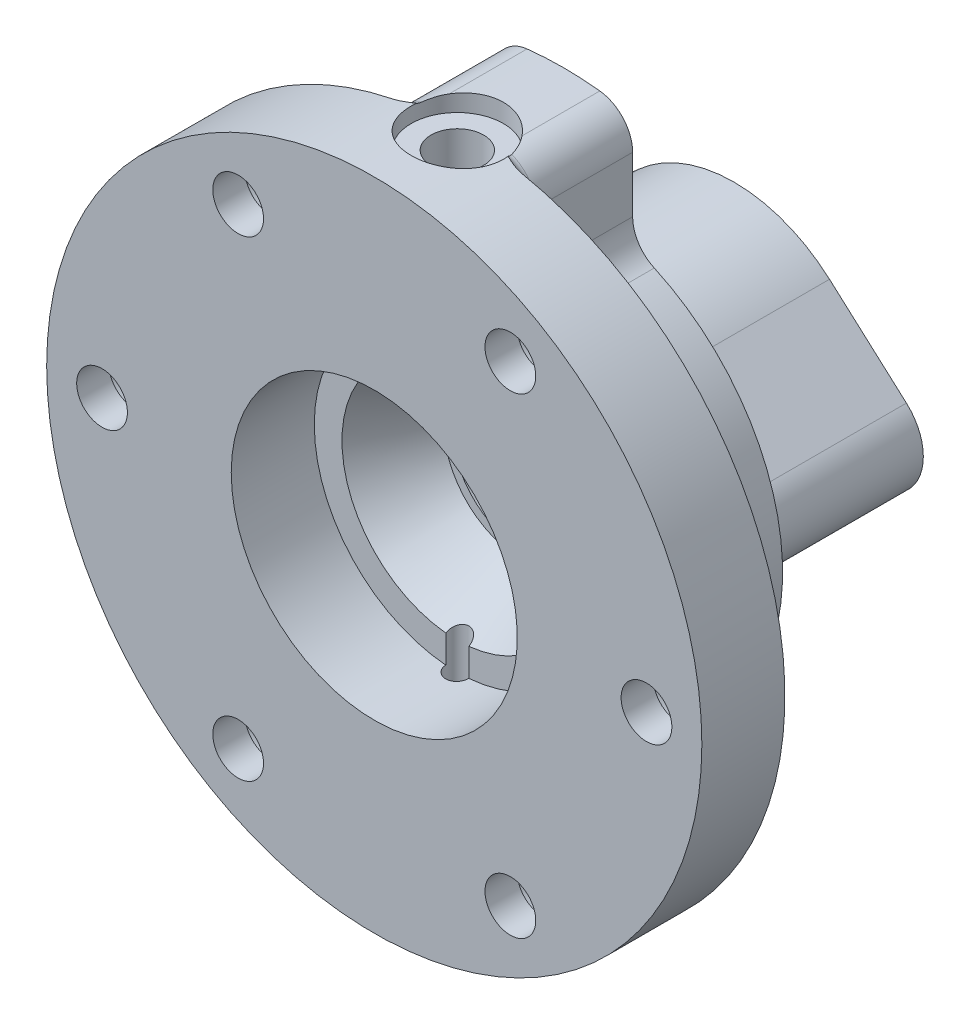
SolidWorks part; units mm, degrees
ref_plane "Piano frontale" through (0, 0, 0) normal (0, 0, 1) x (1, 0, 0)
ref_plane "Piano superiore" through (0, 0, 0) normal (0, 1, 0) x (1, 0, 0)
ref_plane "Piano destro" through (0, 0, 0) normal (1, 0, 0) x (0, 0, -1)
sketch "Schizzo1" plane through (0, 0, 0) normal (0, 1, 0) x (1, 0, 0)
  line L0 (0, 44.9759) -> (0, -36.1533) construction
  line L1 (-15.5, 0) -> (-35.5, 0)
  line L2 (-55, 0) -> (55, 0) construction
  line L3 (-35.5, 0) -> (-35.5, 20.5)
  line L4 (-35.5, 20.5) -> (-7.5, 20.5)
  line L5 (-7.5, 20.5) -> (-7.5, 16)
  line L6 (-7.5, 16) -> (-8.4585, 16)
  line L7 (-8.4585, 16) -> (-12.5, 9)
  line L8 (-12.5, 9) -> (-15.5, 9)
  line L9 (-15.5, 9) -> (-15.5, 0)
  point P3 (-11.0457, 18.3109)
  point P7 (-12.3203, 13.9449)
  dimension "D1" = 15
  dimension "D2" = 20.5
  dimension "D3" = 7
  dimension "D4" = 30
  dimension "D5" = 25
  dimension "D6" = 31
  dimension "D7" = 71
  dimension "D8" = 9
revolve "Rivoluzione1" add sketch "Schizzo1" angle 360 about L0
sketch "Schizzo3" plane through (0, 0, -20.5) normal (0, 0, -1) x (-1, 0, 0)
  line L0 (0, 35.5) -> (0, -35.5) construction
  line L1 (-7.5, 34.6987) -> (-7.5, 22.5347)
  line L2 (-7.5, -22.5347) -> (-7.5, -34.6987)
  circle A0 centre (0, 0) radius 35.5 construction
  arc A1 (-7.5, 22.5347) -> (-7.5, -22.5347) centre (0, 0) ccw
  point P9 (0, 0)
  circle M3 centre (0, 0) radius 35.5
  dimension "D2" = 47.5
  dimension "D1" = 15
extrude "Taglio-Estrusione1" cut sketch "Schizzo3" against normal blind 11.5 and the other way through all contours A1 L1 L2 M3 region at (8.2483, 28.6167, -20.5)
mirror "Specchia1" about plane through (0, 0, 0) normal (1, 0, 0) of "Taglio-Estrusione1"
sketch "Schizzo4" plane through (0, 0, -20.5) normal (0, 0, -1) x (-1, 0, 0)
  line L0 (-23.75, 0) -> (23.75, 0) construction
  line L5 (0, 0) -> (0, -20.8425) construction
  line L6 (-18.6667, 4.0995) -> (-10.3333, 11.553)
  line L7 (18.6667, 4.0995) -> (10.3333, 11.553)
  line L8 (18.6667, -4.0995) -> (10.3333, -11.553)
  line L10 (-18.6667, -4.0995) -> (-10.3333, -11.553)
  arc A0 (-7.5, 22.5347) -> (-7.5, -22.5347) centre (0, 0) ccw construction
  arc A1 (7.5, -22.5347) -> (7.5, 22.5347) centre (0, 0) ccw construction
  circle A2 centre (0, 0) radius 11.5
  arc A7 (-10.3333, -11.553) -> (10.3333, -11.553) centre (0, 0) ccw
  arc A8 (-18.6667, 4.0995) -> (-18.6667, -4.0995) centre (-15, 0) ccw
  arc A9 (18.6667, 4.0995) -> (18.6667, -4.0995) centre (15, 0) cw
  arc A10 (10.3333, 11.553) -> (-10.3333, 11.553) centre (0, 0) ccw
  point P11 (18.6667, -4.0995)
  point P19 (-10.2774, 11.6028)
  point P24 (18.7896, -4.0995)
  point P27 (-19.3805, 3.3258)
  dimension "D1" = 23
  dimension "D2" = 31
  dimension "D3" = 5.5
  dimension "D4" = 30
extrude "Estrusione-Estrusione1" add sketch "Schizzo4" along normal blind 18.5
fillet "Raccordo1" radius 4 8 edges at (-7.5, -34.6987, -14.75) (-7.5, -22.5347, -14.75) (7.5, -34.6987, -14.75) (7.5, -22.5347, -14.75) (7.5, 22.5347, -14.75) (7.5, 34.6987, -14.75) (-7.5, 34.6987, -14.75) (-7.5, 22.5347, -14.75)
fillet "Raccordo2" radius 1 14 edges at (8.1362, 23.0905, -9) (7.5, 28.28, -9) (6.4814, 33.9716, -9) (-6.4814, 33.9716, -9) (-7.5, 28.28, -9) (-8.1362, 23.0905, -9) (6.4814, -33.9716, -9) (7.5, -28.28, -9) (8.1362, -23.0905, -9) (-6.4814, -33.9716, -9) (-7.5, -28.28, -9) (-8.1362, -23.0905, -9) (-23.75, 0, -9) (23.75, 0, -9)
fillet "Raccordo3" radius 2 8 edges at (20.5, 0, -20.5) (14.5, -7.8262, -20.5) (0, 15.5, -20.5) (14.5, 7.8262, -20.5) (-14.5, 7.8262, -20.5) (-20.5, 0, -20.5) (-14.5, -7.8262, -20.5) (0, -15.5, -20.5)
hole_wizard "Foro Ø5.0 (5)-1" positions "Schizzo6" profile "Schizzo7" hole size "Ø5.0" standard "ISO"
sketch "Schizzo6" plane through (0, 0, -39) normal (0, 0, -1) x (-1, 0, 0)
  point P0 (-15, 0)
  point P3 (15, 0)
sketch "Schizzo7" plane through (15, 0, -39) normal (1, 0, 0) x (0, 1, 0)
  line L0 (0, 0) -> (0, 9.0022)
  line L1 (0, 9.0022) -> (2.5, 7.5)
  line L2 (2.5, 7.5) -> (2.5, 0.025)
  line L3 (2.5, 0.025) -> (2.525, 0)
  line L5 (2.525, 0) -> (0, 0)
  line L6 (-2.5, 0.025) -> (-2.525, 0) construction
  line L10 (0, 9.0022) -> (-2.5, 7.5) construction
  line L11 (0, -6.35) -> (0, 107.95) construction
  dimension "Hole Dia." = 5
  dimension "Hole Depth" = 7.5
  dimension "Near C'Sink Dia." = 5.05
  dimension "Near C'Sink Angle" = 90
  dimension "Drill Angle" = 118
ref_point "Punto1"
ref_plane "Piano2" through (0, -35.5, 0) normal (0, 1, 0) x (1, 0, 0)
hole_wizard "Foro Ø2.5 (2.5)-1" positions "Schizzo9" profile "Schizzo10" hole size "Ø2.5" standard "ISO"
sketch "Schizzo9" plane through (0, -35.5, 0) normal (0, 1, 0) x (1, 0, 0)
  line L0 (0, 0) -> (0, 11.1259) construction
  line L1 (-35.5, 0) -> (35.5, 0) construction
  point P6 (0, 9)
  dimension "D1" = 9
sketch "Schizzo10" plane through (0, -35.5, -9) normal (1, 0, 0) x (0, 0, -1)
  line L0 (0, 0) -> (0, 36.2501)
  line L1 (0, 36.2501) -> (1.25, 35.499)
  line L2 (1.25, 35.499) -> (1.25, 0.025)
  line L3 (1.25, 0.025) -> (1.275, 0)
  line L5 (1.275, 0) -> (0, 0)
  line L6 (-1.25, 0.025) -> (-1.275, 0) construction
  line L10 (0, 36.2501) -> (-1.25, 35.499) construction
  line L11 (0, -6.35) -> (0, 107.95) construction
  dimension "Hole Dia." = 2.5
  dimension "Hole Depth" = 35.499
  dimension "Near C'Sink Dia." = 2.55
  dimension "Near C'Sink Angle" = 90
  dimension "Drill Angle" = 118
hole_wizard "Foro lamato per Bullone M5 a testa esagonale-1" positions "Schizzo11" profile "Schizzo12" counterbore size "M5" standard "ISO"
sketch "Schizzo11" plane through (0, -35.5, 0) normal (0, 1, 0) x (1, 0, 0)
  line L0 (-15.5, 9) -> (15.5, 9) construction
  point P0 (0, 9)
sketch "Schizzo12" plane through (0, -35.5, -9) normal (1, 0, 0) x (0, 0, -1)
  line L0 (0, 0) -> (0, 17.7125)
  line L1 (0, 17.7125) -> (2.85, 16)
  line L2 (2.85, 16) -> (2.85, 2)
  line L3 (2.85, 2) -> (5, 2)
  line L4 (5, 2) -> (5, 0)
  line L5 (5, 0) -> (0, 0)
  line L10 (0, 17.7125) -> (-2.85, 16) construction
  line L11 (0, -6.35) -> (0, 107.95) construction
  dimension "Hole Dia." = 5.7
  dimension "Hole Depth" = 16
  dimension "C'Bore Dia." = 10
  dimension "C'Bore Depth" = 2
  dimension "Drill Angle" = 118
mirror "Specchia2" about plane through (0, 0, 0) normal (0, 1, 0) of "Foro lamato per Bullone M5 a testa esagonale-1", "Foro Ø2.5 (2.5)-1"
hole_wizard "Foro Ø2.5 (2.5)-2" positions "Schizzo13" profile "Schizzo14" hole size "Ø2.5" standard "ISO" end condition up to next
sketch "Schizzo13" plane through (0, 0, -20.5) normal (0, 0, -1) x (-1, 0, 0)
  line L2 (0, 0) -> (9.3711, 0) construction
  line L4 (0, -23) -> (0, 23) construction
  point P25 (0, 23)
  point P27 (0, -23)
  dimension "D1" = 46
sketch "Schizzo14" plane through (0, -23, -20.5) normal (1, 0, 0) x (0, 1, 0)
  line L0 (0, 0) -> (0, 8.65)
  line L1 (0, 8.65) -> (1.25, 8.65)
  line L2 (1.25, 8.65) -> (1.25, 0)
  line L5 (1.25, 0) -> (0, 0)
  line L11 (0, -6.35) -> (0, 107.95) construction
  dimension "Thru Hole Dia." = 2.5
  dimension "Thru Hole Depth" = 8.65
hole_wizard "Foro lamato per Bullone M5 a testa esagonale-3" positions "Schizzo17" profile "Schizzo18" counterbore size "M5" standard "ISO" end condition up to next
sketch "Schizzo17" plane through (0, 0, -9) normal (0, 0, -1) x (-1, 0, 0)
  line L1 (0, 0) -> (29.5, 0) construction
  circle A0 centre (0, 0) radius 29.5 construction
  point P9 (29.5, 0)
  dimension "D1" = 59
sketch "Schizzo18" plane through (-29.5, 0, -9) normal (1, 0, 0) x (0, 1, 0)
  line L0 (0, 0) -> (0, 9)
  line L1 (0, 9) -> (2.75, 9)
  line L3 (2.75, 9) -> (2.75, 5.5)
  line L4 (2.75, 5.5) -> (4.5, 5.5)
  line L5 (4.5, 5.5) -> (4.5, 0)
  line L7 (4.5, 0) -> (0, 0)
  line L11 (0, -6.35) -> (0, 107.95) construction
  dimension "Thru Hole Dia." = 5.5
  dimension "Thru Hole Depth" = 9
  dimension "C'Bore Dia." = 9
  dimension "C'Bore Depth" = 5.5
pattern_circular "RipetizioneCircolare1" count 6 over 360 about axis through (0, 0, -39) along (0, 0, 1) of "Foro lamato per Bullone M5 a testa esagonale-3" reverse direction yes
sketch "Schizzo19" plane through (0, 0, 0) normal (0, 0, 1) x (1, 0, 0)
  line L0 (0, 0) -> (25.2415, 0)
